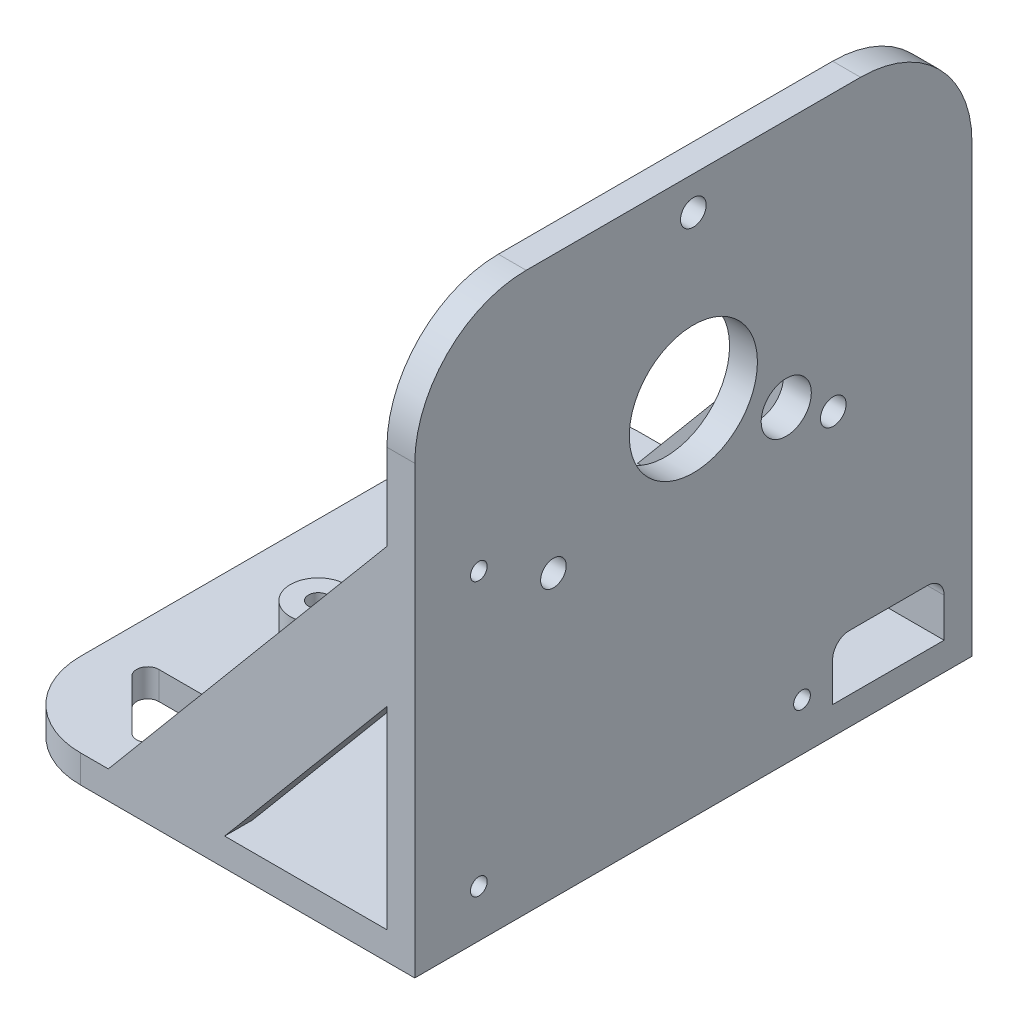
SolidWorks part; units mm, degrees
ref_plane "前视基准面" through (0, 0, 0) normal (0, 0, 1) x (1, 0, 0)
ref_plane "上视基准面" through (0, 0, 0) normal (0, 1, 0) x (1, 0, 0)
ref_plane "右视基准面" through (0, 0, 0) normal (1, 0, 0) x (0, 0, -1)
sketch "草图1" plane through (0, 0, 0) normal (0, 1, 0) x (1, 0, 0)
  line L1 (-35, -35) -> (35, -35)
  line L2 (-35, -35) -> (-35, 35)
  line L3 (-35, 35) -> (35, 35)
  line L4 (35, -35) -> (35, 35)
  line L5 (-35, -35) -> (35, 35) construction
  line L6 (-35, 35) -> (35, -35) construction
  point P0 (0, 0)
  dimension "D1" = 70
  dimension "D2" = 70
extrude "凸台-拉伸1" add sketch "草图1" along normal blind 5
sketch "草图2" plane through (0, 5, 0) normal (0, 1, 0) x (1, 0, 0)
  line L0 (0, 0) -> (0, 20)
  line L1 (0, 0) -> (17.3205, -10)
  line L2 (0, 0) -> (-17.3205, -10)
  circle A0 centre (0, 0) radius 20
  dimension "D1" = 40
  dimension "D2" = 120
  dimension "D3" = 120
sketch "草图3" plane through (0, 5, 0) normal (0, 1, 0) x (1, 0, 0)
  point P0 (0, 20)
  point P3 (-17.3205, -10)
  point P6 (17.3205, -10)
hole_wizard "孔1" positions "草图3" profile "草图4" legacy end condition up to next
sketch "草图4" plane through (0, 5, -20) normal (1, 0, 0) x (0, 0, 1)
  line L0 (0, 0) -> (0, 5)
  line L1 (0, 5) -> (1.75, 5)
  line L2 (1.75, 5) -> (1.75, 0)
  line L3 (1.75, 0) -> (0, 0)
  line L4 (0, 110) -> (0, -10) construction
  dimension "直径" = 3.5
  dimension "深度" = 5
sketch "草图5" plane through (0, 5, 0) normal (0, 1, 0) x (1, 0, 0)
  point P0 (0, 0)
hole_wizard "孔2" positions "草图5" profile "草图6" legacy end condition up to next
sketch "草图6" plane through (0, 5, 0) normal (1, 0, 0) x (0, 0, 1)
  line L0 (0, 0) -> (0, 5)
  line L1 (0, 5) -> (11.5, 5)
  line L2 (11.5, 5) -> (11.5, 0)
  line L3 (11.5, 0) -> (0, 0)
  line L4 (0, 110) -> (0, -10) construction
  dimension "直径" = 23
  dimension "深度" = 5
sketch "草图7" plane through (35, 0, 0) normal (1, 0, 0) x (0, 0, -1)
  line L1 (-35, 0) -> (35, 0)
  line L2 (-35, 0) -> (-35, 100)
  line L3 (-35, 100) -> (35, 100)
  line L4 (35, 0) -> (35, 100)
  dimension "D1" = 70
  dimension "D2" = 100
extrude "凸台-拉伸2" add sketch "草图7" along normal blind 5 contours L2 L3 L4 L1
sketch "草图11" plane through (40, 0, 0) normal (1, 0, 0) x (0, 0, -1)
  line L0 (35, 0) -> (35, 100) construction
  line L1 (-35, 100) -> (35, 100)
  line L2 (-35, 100) -> (-35, 30)
  line L3 (-35, 30) -> (35, 30)
  line L4 (35, 100) -> (35, 30)
  line L5 (-35, 100) -> (35, 30)
  line L6 (0, 65) -> (0, 94)
  line L7 (0, 65) -> (-25.1147, 50.5)
  line L8 (0, 65) -> (25.1147, 50.5)
  circle A0 centre (0, 65) radius 29
  dimension "D2" = 58
  dimension "D1" = 70
  dimension "D3" = 120
  dimension "D4" = 120
sketch "草图12" plane through (40, 0, 0) normal (1, 0, 0) x (0, 0, -1)
  point P0 (0, 94)
  point P3 (-25.1147, 50.5)
  point P6 (25.1147, 50.5)
hole_wizard "孔4" positions "草图12" profile "草图13" legacy end condition up to next
sketch "草图13" plane through (40, 94, 0) normal (0, 1, 0) x (0, 0, -1)
  line L0 (0, 0) -> (0, 5)
  line L1 (0, 5) -> (2.3, 5)
  line L2 (2.3, 5) -> (2.3, 0)
  line L3 (2.3, 0) -> (0, 0)
  line L4 (0, 110) -> (0, -10) construction
  dimension "直径" = 4.6
  dimension "深度" = 5
hole_wizard "孔5" positions "草图14" profile "草图15" legacy end condition up to next
sketch "草图14" plane through (40, 0, 0) normal (1, 0, 0) x (0, 0, -1)
  point P0 (0, 65)
sketch "草图15" plane through (40, 65, 0) normal (0, 1, 0) x (0, 0, -1)
  line L0 (0, 0) -> (0, 5)
  line L1 (0, 5) -> (11.5, 5)
  line L2 (11.5, 5) -> (11.5, 0)
  line L3 (11.5, 0) -> (0, 0)
  line L4 (0, 110) -> (0, -10) construction
  dimension "直径" = 23
  dimension "深度" = 5
sketch "草图16" plane through (0, 5, 0) normal (0, 1, 0) x (1, 0, 0)
  circle A0 centre (0, 20) radius 5
  circle A1 centre (-17.3205, -10) radius 5
  circle A2 centre (17.3205, -10) radius 5
  circle A3 centre (0, 20) radius 1.75
  circle A4 centre (-17.3205, -10) radius 1.75
  circle A5 centre (17.3205, -10) radius 1.75
  dimension "D1" = 10
  dimension "D2" = 10
  dimension "D3" = 10
  dimension "D4" = 3.5
  dimension "D5" = 3.5
  dimension "D6" = 3.5
extrude "凸台-拉伸3" add sketch "草图16" along normal blind 5
sketch "草图17" plane through (0, 0, -35) normal (0, 0, -1) x (-1, 0, 0)
  line L0 (-40, 40) -> (0, 0)
  line L1 (-40, 0) -> (0, 0)
  line L2 (-40, 0) -> (-40, 40)
  line L3 (-40, 40) -> (0, 40)
  line L4 (0, 0) -> (0, 40)
  line L5 (-35, 5) -> (-35, 100) construction
  line L6 (-40, 100) -> (-35, 100)
  line L7 (-40, 100) -> (-40, 40)
  line L8 (-40, 40) -> (-35, 40)
  line L9 (-35, 100) -> (-35, 40)
  line L11 (0, 0) -> (35, 0)
  line L12 (0, 0) -> (0, 5)
  line L13 (0, 5) -> (35, 5)
  line L14 (35, 0) -> (35, 5)
  line M3 (-40, 0) -> (35, 0)
  line M4 (35, 0) -> (35, 5)
  line M5 (35, 5) -> (-35, 5)
  line M6 (-35, 5) -> (-35, 100)
  line M7 (-35, 100) -> (-40, 100)
  line M8 (-40, 100) -> (-40, 0)
  dimension "D1" = 40
  dimension "D2" = 40
sketch "草图18" plane through (0, 0, 35) normal (0, 0, 1) x (1, 0, 0)
  line L0 (40, 40) -> (0, 0)
  line L1 (40, 0) -> (0, 0)
  line L2 (40, 0) -> (40, 40)
  line L3 (40, 40) -> (0, 40)
  line L4 (0, 0) -> (0, 40)
  line L6 (40, 40) -> (35, 40)
  line L7 (40, 40) -> (40, 100)
  line L8 (40, 100) -> (35, 100)
  line L9 (35, 40) -> (35, 100)
  line L10 (-35, 5) -> (0, 5)
  line L11 (-35, 5) -> (-35, 0)
  line L12 (-35, 0) -> (0, 0)
  line L13 (0, 5) -> (0, 0)
  line M3 (-35, 0) -> (40, 0)
  line M4 (40, 0) -> (40, 100)
  line M5 (40, 100) -> (35, 100)
  line M6 (35, 100) -> (35, 5)
  line M7 (35, 5) -> (-35, 5)
  line M8 (-35, 5) -> (-35, 0)
  dimension "D1" = 40
  dimension "D2" = 40
extrude "凸台-拉伸4" add sketch "草图17" along normal blind 15 contours L3 M8 M6 M7 | L0 M8 M3 M5 M6 | L3 L0 M6 | L4 M3 M4 M5 | L0 L4 M5
extrude "凸台-拉伸5" add sketch "草图18" along normal blind 15 contours L4 M3 M7 M8 | L4 L0 M7 | L0 M4 M6 M7 M3 | L0 L3 M6 | L3 M4 M5 M6
sketch "草图19" plane through (0, 0, -50) normal (0, 0, -1) x (-1, 0, 0)
  line L0 (15, 5) -> (-35, 64.5877)
  line L1 (0, 5) -> (17.3205, 5) construction
  line L2 (20, 5) -> (-20, 5) construction
  line L3 (-35, 5) -> (-35, 100) construction
  line L4 (35, 0) -> (35, 5) construction
  line L5 (-35, 64.5877) -> (-35, 5)
  line L6 (-35, 5) -> (15, 5)
  dimension "D1" = 50
  dimension "D2" = 20
extrude "凸台-拉伸6" add sketch "草图19" against normal blind 5
sketch "草图20" plane through (0, 0, 50) normal (0, 0, 1) x (1, 0, 0)
  line L0 (-15, 5) -> (35, 64.5877)
  line L1 (35, 5) -> (-35, 5) construction
  line L2 (35, 100) -> (35, 5) construction
  line L3 (-35, 5) -> (-35, 0) construction
  line L4 (20, 5) -> (-20, 5) construction
  line L5 (35, 64.5877) -> (35, 5)
  line L6 (35, 5) -> (-15, 5)
  dimension "D1" = 20
  dimension "D2" = 50
extrude "凸台-拉伸7" add sketch "草图20" against normal blind 5
sketch "草图21" plane through (40, 0, 0) normal (1, 0, 0) x (0, 0, -1)
  line L0 (-50, 0) -> (-50, 100) construction
  line L1 (-50, 0) -> (50, 0)
  line L2 (-50, 0) -> (-50, 5)
  line L3 (-50, 5) -> (50, 5)
  line L4 (50, 0) -> (50, 5)
  line L5 (50, 5) -> (-50, 5)
  line L6 (50, 5) -> (50, 61)
  line L7 (50, 61) -> (-50, 61)
  line L8 (-50, 5) -> (-50, 61)
  line L10 (-42, 61) -> (43, 61)
  line L11 (-42, 61) -> (-42, 5)
  line L12 (-42, 5) -> (43, 5)
  line L13 (43, 61) -> (43, 5)
  line L14 (-38.5, 8.5) -> (19.5, 8.5)
  line L15 (-38.5, 8.5) -> (-38.5, 57.5)
  line L16 (-38.5, 57.5) -> (19.5, 57.5)
  line L17 (19.5, 8.5) -> (19.5, 57.5)
  dimension "D1" = 56
  dimension "D2" = 8
  dimension "D3" = 85
  dimension "D4" = 3.5
  dimension "D5" = 3.5
  dimension "D6" = 58
  dimension "D7" = 49
sketch "草图22" plane through (40, 0, 0) normal (1, 0, 0) x (0, 0, -1)
  point P0 (-38.5, 57.5)
  point P3 (-38.5, 8.5)
  point P6 (19.5, 8.5)
hole_wizard "孔6" positions "草图22" profile "草图23" legacy end condition up to next
sketch "草图23" plane through (40, 57.5, 38.5) normal (0, 1, 0) x (0, 0, -1)
  line L0 (0, 0) -> (0, 5)
  line L1 (0, 5) -> (1.5, 5)
  line L2 (1.5, 5) -> (1.5, 0)
  line L3 (1.5, 0) -> (0, 0)
  line L4 (0, 110) -> (0, -10) construction
  dimension "直径" = 3
  dimension "深度" = 5
fillet "圆角2" radius 20 2 edges at (37.5, 100, 50) (37.5, 100, -50)
sketch "草图24" plane through (35, 0, 0) normal (-1, 0, 0) x (0, 0, 1)
  line L0 (0, 65) -> (-16.671, 55.375)
  line L1 (0, 65) -> (-25.1147, 50.5) construction
  circle A0 centre (0, 65) radius 19.25
  dimension "D1" = 38.5
sketch "草图25" plane through (35, 0, 0) normal (-1, 0, 0) x (0, 0, 1)
  point P0 (-16.671, 55.375)
hole_wizard "孔7" positions "草图25" profile "草图26" legacy end condition up to next
sketch "草图26" plane through (35, 55.375, -16.671) normal (0, 1, 0) x (0, 0, 1)
  line L0 (0, 0) -> (0, 5)
  line L1 (0, 5) -> (4.5, 5)
  line L2 (4.5, 5) -> (4.5, 0)
  line L3 (4.5, 0) -> (0, 0)
  line L4 (0, 110) -> (0, -10) construction
  dimension "直径" = 9
  dimension "深度" = 5
sketch "草图28" plane through (0, 5, 0) normal (0, 1, 0) x (1, 0, 0)
  line L0 (-35, 30) -> (-15, 50)
  line L1 (-35, -50) -> (-15, -50)
  line L2 (-35, -50) -> (-35, -30)
  line L3 (-35, -30) -> (-15, -30)
  line L4 (-15, -50) -> (-15, -30)
  line L5 (-35, 50) -> (-15, 50)
  line L6 (-35, 50) -> (-35, 30)
  line L7 (-35, 30) -> (-15, 30)
  line L8 (-15, 50) -> (-15, 30)
  line L9 (-30.7574, 30) -> (-15, 45.7574)
  line L10 (-35, -30) -> (-15, -50)
  line L11 (-30.7574, -30) -> (-15, -45.7574)
  dimension "D1" = 20
  dimension "D2" = 20
  dimension "D3" = 20
  dimension "D4" = 20
  dimension "D5" = 3
  dimension "D6" = 3
extrude "切除-拉伸1" cut sketch "草图28" against normal blind 10 contours L9 L7 L8 | L3 L11 L4
fillet "圆角3" radius 2 6 edges at (-30.7574, 2.5, 30) (-15, 2.5, 45.7574) (-15, 2.5, 30) (-30.7574, 2.5, -30) (-15, 2.5, -30) (-15, 2.5, -45.7574)
fillet "圆角4" radius 15 2 edges at (-35, 2.5, 50) (-35, 2.5, -50)
sketch "草图29" plane through (40, 0, 0) normal (1, 0, 0) x (0, 0, -1)
  line L0 (50, 5) -> (50, 61) construction
  line L1 (25, 15) -> (45, 15)
  line L2 (25, 15) -> (25, 5)
  line L3 (25, 5) -> (45, 5)
  line L4 (45, 15) -> (45, 5)
  line L5 (-50, 0) -> (50, 0) construction
  dimension "D1" = 5
  dimension "D2" = 5
  dimension "D3" = 20
  dimension "D4" = 10
extrude "切除-拉伸2" cut sketch "草图29" against normal blind 10
fillet "圆角5" radius 3 2 edges at (37.5, 15, -45) (37.5, 15, -25)
sketch "草图30" plane through (0, 5, 0) normal (0, 1, 0) x (1, 0, 0)
  line L0 (-27.3431, 33.4142) -> (-18.4142, 42.3431)
  line L1 (-22.8787, 37.8787) -> (-27.1213, 42.1213)
  line L2 (-27.1213, 42.1213) -> (-22.8787, 46.364)
  line L3 (-22.8787, 46.364) -> (-31.364, 37.8787)
  dimension "D1" = 90
  dimension "D2" = 6
  dimension "D3" = 6
  dimension "D4" = 12
sketch "草图31" plane through (0, 5, 0) normal (0, 1, 0) x (1, 0, 0)
  line L0 (-22.8787, 46.364) -> (-31.364, 37.8787) construction
  point P0 (-31.364, 37.8787)
  point P3 (-27.1213, 42.1213)
  point P7 (-22.8787, 46.364)
hole_wizard "孔8" positions "草图31" profile "草图32" legacy end condition up to next
sketch "草图32" plane through (-31.364, 5, -37.8787) normal (1, 0, 0) x (0, 0, 1)
  line L0 (0, 0) -> (0, 5)
  line L1 (0, 5) -> (1.65, 5)
  line L2 (1.65, 5) -> (1.65, 0)
  line L3 (1.65, 0) -> (0, 0)
  line L4 (0, 110) -> (0, -10) construction
  dimension "直径" = 3.3
  dimension "深度" = 5
sketch "草图34" plane through (0, 0, 50) normal (0, 0, 1) x (1, 0, 0)
  line L0 (35, 64.5877) -> (35, 5)
  line L2 (-20, 0) -> (40, 0) construction
  line L3 (35, 5) -> (-15, 5)
  line L4 (35, 84.25) -> (35, 45.75) construction
  line L5 (-15, 5) -> (35, 64.5877)
  line L6 (20, 5) -> (-20, 5) construction
  line L7 (35, 39.6961) -> (5.8865, 5)
  dimension "D1" = 5
  dimension "D2" = 16
extrude "切除-拉伸3" cut sketch "草图34" against normal up to next contours L0 L7 L3
